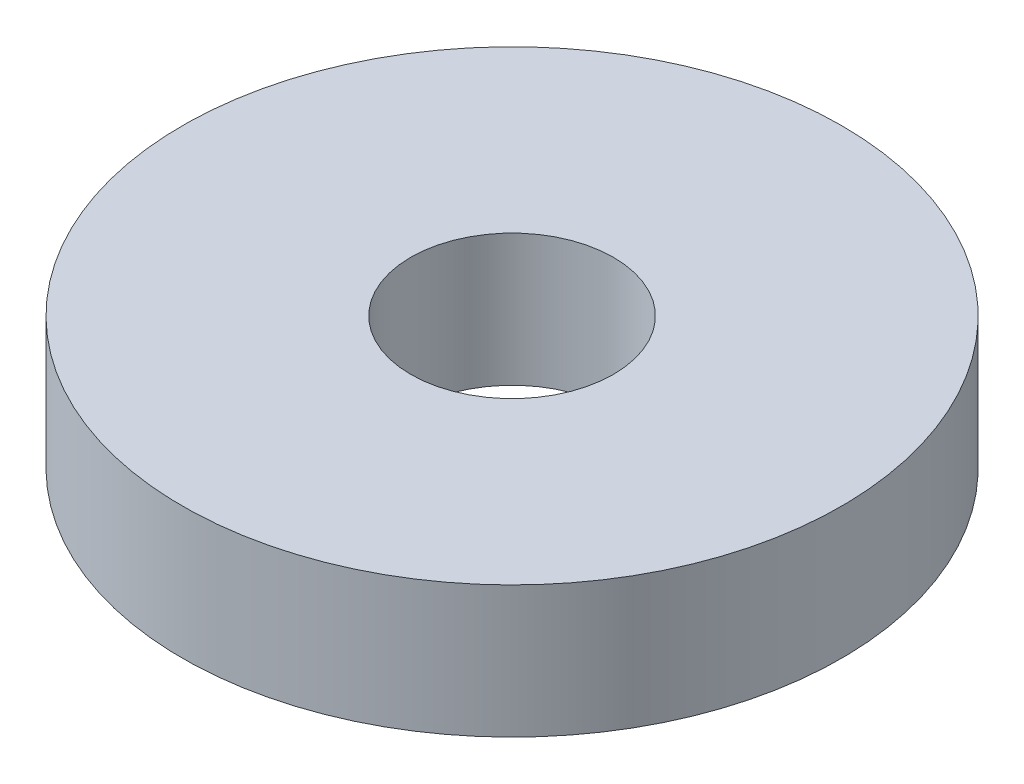
SolidWorks part; units mm, degrees
ref_plane "Front Plane" through (0, 0, 0) normal (0, 0, 1) x (1, 0, 0)
ref_plane "Top Plane" through (0, 0, 0) normal (0, 1, 0) x (1, 0, 0)
ref_plane "Right Plane" through (0, 0, 0) normal (1, 0, 0) x (0, 0, -1)
sketch "Sketch1" plane through (0, 0, 0) normal (0, 1, 0) x (1, 0, 0)
  circle A0 centre (0, 0) radius 65
  dimension "FLANGE_OD" = 130
extrude "Boss-Extrude1" add sketch "Sketch1" along normal blind 26
sketch "Sketch2" plane through (0, 0, 0) normal (0, 1, 0) x (1, 0, 0)
  circle A0 centre (0, 0) radius 20
  dimension "BORE_D" = 40
extrude "Cut-Extrude1" cut sketch "Sketch2" along normal through all
sketch "Sketch3" plane through (0, 26, 0) normal (0, 1, 0) x (1, 0, 0)
  circle A0 centre (0, 0) radius 14.489 construction
  circle A1 centre (-14.489, 0) radius 4.3771
  dimension "BOLT_D" = 8.7543
  dimension "BOLT_PCD" = 28.9779
extrude "Cut-Extrude2" cut sketch "Sketch3" against normal blind 20.966 rebuild error yes
pattern_circular "CirPattern1" count 3 over 360 rebuild error yes
